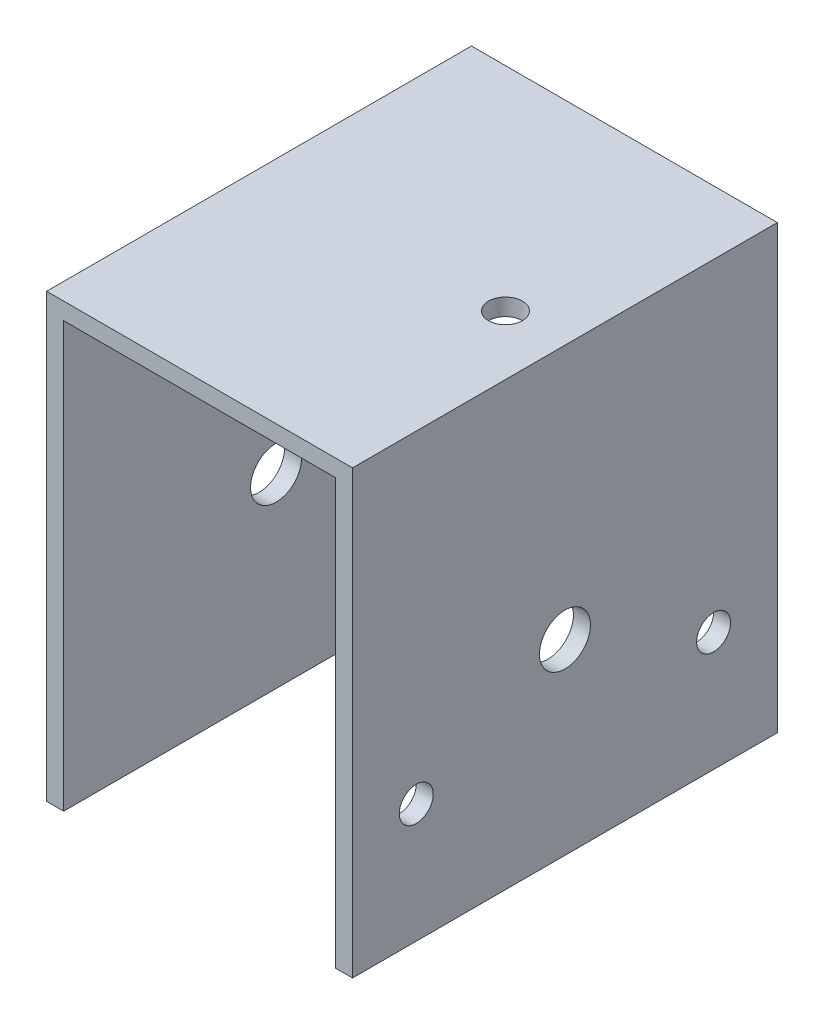
SolidWorks part; units mm, degrees
ref_plane "Front Plane" through (0, 0, 0) normal (0, 0, 1) x (1, 0, 0)
ref_plane "Top Plane" through (0, 0, 0) normal (0, 1, 0) x (1, 0, 0)
ref_plane "Right Plane" through (0, 0, 0) normal (1, 0, 0) x (0, 0, -1)
sketch "Sketch2" plane through (0, 0, 0) normal (0, 1, 0) x (1, 0, 0)
  line L1 (-27, 25) -> (5, 25)
  line L2 (-27, 25) -> (-27, -25)
  line L3 (-27, -25) -> (5, -25)
  line L4 (5, 25) -> (5, -25)
  circle A0 centre (0, 0) radius 2
  dimension "D5" = 4
  dimension "D1" = 32
  dimension "D2" = 50
  dimension "D3" = 5
  dimension "D4" = 25
extrude "Boss-Extrude1" add sketch "Sketch2" along normal blind 2
sketch "Sketch3" plane through (5, 0, 0) normal (1, 0, 0) x (0, 0, -1)
  line L3 (-25, 2) -> (25, 2) construction
  line L4 (25, 0) -> (25, 2)
  line L5 (25, 2) -> (-25, 2)
  line L6 (0, -28) -> (8.8326, -28) construction
  line L7 (25, 0) -> (25, -50)
  line L8 (25, -50) -> (-25, -50)
  line L9 (-25, -50) -> (-25, 2)
  circle A0 centre (0, -28) radius 3
  circle A1 centre (-17.5, -36) radius 2
  circle A2 centre (17.5, -36) radius 2
  dimension "D6" = 6
  dimension "D9" = 4
  dimension "D12" = 4
  dimension "D1" = 30
  dimension "D2" = 50
  dimension "D3" = 25
  dimension "D7" = 17.5
  dimension "D8" = 8
  dimension "D10" = 17.5
  dimension "D11" = 8
sketch "Sketch4" plane through (-27, 0, 0) normal (-1, 0, 0) x (0, 0, 1)
  line L2 (-25, -6.4325) -> (-25, 2)
  line L4 (-25, 2) -> (25, 2)
  line L6 (-25, -4.4325) -> (-25, -54.4325) construction
  line L8 (-25, -50) -> (-25, -6.4325)
  line L9 (25, -50) -> (-25, -50)
  line L10 (25, 2) -> (25, -50)
  line L12 (-25, 0) -> (25, 0) construction
  circle A1 centre (0, -28) radius 3
  circle A2 centre (0, -28) radius 3 construction
  dimension "D1" = 6
  dimension "D3" = 50
  dimension "D2" = 0
  dimension "D5" = 50
extrude "Boss-Extrude2" add sketch "Sketch4" along normal blind 2
extrude "Boss-Extrude3" add sketch "Sketch3" along normal blind 2
equation "\"d\"= 40"
